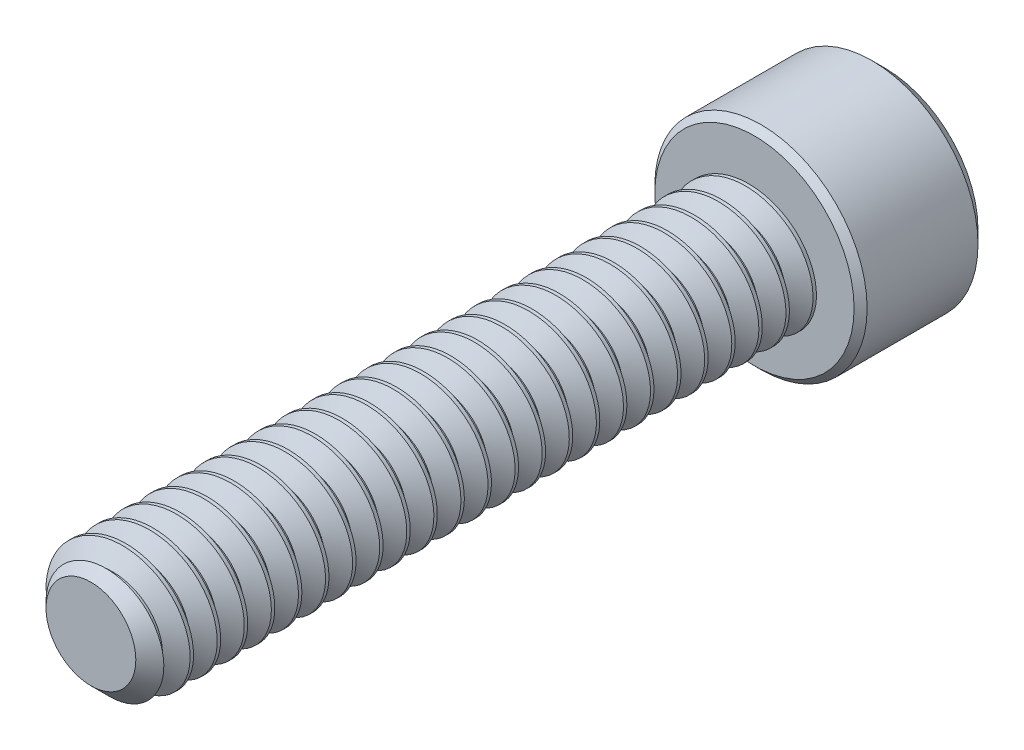
SolidWorks part; units mm, degrees
ref_plane "Front Plane" through (0, 0, 0) normal (0, 0, 1) x (1, 0, 0)
ref_plane "Top Plane" through (0, 0, 0) normal (0, 1, 0) x (1, 0, 0)
ref_plane "Right Plane" through (0, 0, 0) normal (1, 0, 0) x (0, 0, -1)
sketch "Sketch1" plane through (0, 0, 0) normal (0, 0, 1) x (1, 0, 0)
  line L0 (0, 1.0922) -> (0, -1.0922) construction
  circle A0 centre (0, 0) radius 1.0922
  dimension "OD" = 2.1844
extrude "Extrude1" add sketch "Sketch1" against normal blind 11.1125
sketch "Sketch2" plane through (0, 0, 0) normal (0, 0, 1) x (1, 0, 0)
  circle A0 centre (0, 0) radius 1.0922 construction
  circle A1 centre (0, 0) radius 1.0922
curve "Helix/Spiral1" pitch 0.4536 height 11.5661 turns 25.5 parameters "pitch"=0.4536
chamfer "Chamfer3" distance 0.3402 angle 45 1 edges at (1.0922, 0, 0)
sketch "Sketch3" plane through (0, 0, 0) normal (1, 0, 0) x (0, 0, -1)
  line L0 (-0.3969, 1.0922) -> (-0.2268, 0.7976)
  line L1 (-0.2268, 0.7976) -> (-0.1701, 0.7976)
  line L2 (-0.1701, 0.7976) -> (0, 1.0922)
  line L3 (-0.3969, 1.0922) -> (0, 1.0922)
  line L4 (-0.1984, 1.0922) -> (-0.1984, 0.7976) construction
  line L5 (-0.3118, 0.9449) -> (-0.085, 0.9449) construction
  line L6 (0, 1.0922) -> (0, -1.0922) construction
  dimension "D1" = 0.0567
  dimension "D2" = 0.2268
  dimension "D3" = 60
sweep "Cut-Sweep1" cut profiles "Sketch3" path "Helix/Spiral1" align with end faces yes
sketch "Sketch6" plane through (0, 0, -11.1125) normal (0, 0, -1) x (-1, 0, 0)
  circle A0 centre (0, 0) radius 1.778
  dimension "head dia" = 3.556
extrude "Extrude2" add sketch "Sketch6" along normal blind 2.1844
sketch "Sketch7" plane through (0, 0, -13.2969) normal (0, 0, -1) x (-1, 0, 0)
  line L1 (0, 1.1457) -> (-0.9922, 0.5728)
  line L2 (-0.9922, 0.5728) -> (-0.9922, -0.5728)
  line L3 (-0.9922, -0.5728) -> (0, -1.1457)
  line L4 (0, -1.1457) -> (0.9922, -0.5728)
  line L5 (0.9922, -0.5728) -> (0.9922, 0.5728)
  line L6 (0.9922, 0.5728) -> (0, 1.1457)
  circle A0 centre (0, 0) radius 0.9922 construction
  dimension "hex dia" = 1.9844
extrude "Cut-Extrude1" cut sketch "Sketch7" against normal blind 1.4883
sketch "Sketch8" plane through (0, 0, -13.2969) normal (0, 0, -1) x (-1, 0, 0)
  circle A0 centre (0, 0) radius 1.1457
extrude "Cut-Extrude2" cut sketch "Sketch8" against normal blind 0.2184 draft 45
chamfer "Chamfer1" distance 0.2184 angle 45 1 edges at (-1.778, 0, -13.2969)
chamfer "Chamfer2" distance 0.1092 angle 45 1 edges at (-1.778, 0, -11.1125)
sketch "Sketch9" plane through (0, 0, 0) normal (1, 0, 0) x (0, 0, -1)
  line L0 (0, 1.0922) -> (0, -1.0922) construction
  line L1 (2.4946, 1.0922) -> (2.4946, -1.0922) construction
  line L2 (11.1125, 1.778) -> (11.1125, -1.778) construction
  line L3 (13.2969, 1.778) -> (13.2969, -1.778) construction
  line L4 (13.2969, 0) -> (0, 0) construction
  dimension "D1" = 2.4946
  dimension "D2" = 2.1844
  dimension "D3" = 3.556
  dimension "D4" = 11.1125
equation "\"D3@Helix/Spiral1\" = \"screw length@Extrude1\"+\"pitch@Helix/Spiral1\""
equation "\"D1@Sketch3\" = \"pitch@Helix/Spiral1\"*.125"
equation "\"D2@Sketch3\" = \"pitch@Helix/Spiral1\"*.5"
equation "\"D1@Cut-Extrude1\" = \"hex dia@Sketch7\"*.75"
equation "\"D1@Chamfer1\" = \"head depth@Extrude2\"/10"
equation "\"D1@Sketch9\" = \"pitch@Helix/Spiral1\"*5.5"
equation "\"D1@Chamfer2\" = \"D1@Chamfer1\"/2"
equation "\"D1@Cut-Extrude2\" = \"D1@Chamfer2\"*2"
equation "\"D1@Chamfer3\" = \"pitch@Helix/Spiral1\"*.750"
equation "\"D2@Sketch9\" = \"head depth@Extrude2\""
equation "\"D3@Sketch9\" = \"head dia@Sketch6\""
equation "\"D4@Sketch9\" = \"screw length@Extrude1\""
